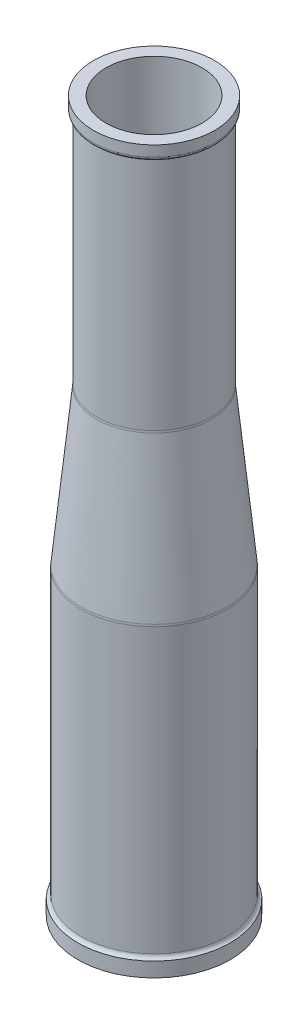
SolidWorks part; units mm, degrees
ref_plane "Alzado" through (0, 0, 0) normal (0, 0, 1) x (1, 0, 0)
ref_plane "Planta" through (0, 0, 0) normal (0, 1, 0) x (1, 0, 0)
ref_plane "Vista lateral" through (0, 0, 0) normal (1, 0, 0) x (0, 0, -1)
sketch "Croquis1" plane through (0, 0, 0) normal (0, 1, 0) x (1, 0, 0)
  circle A0 centre (0, 0) radius 35
  dimension "D1" = 70
extrude "Saliente-Extruir1" add sketch "Croquis1" along normal blind 145
ref_plane "Plano1" through (0, 220, 0) normal (0, 1, 0) x (1, 0, 0)
sketch "Croquis2" plane through (0, 220, 0) normal (0, 1, 0) x (1, 0, 0)
  circle A2 centre (0, 0) radius 27.5
  dimension "D1" = 55
loft "Recubrir1" add profiles "Croquis2" section edge at (0, 145, 35) section "Croquis2" connector at (-33.8055, 145, 9.0657) connector at (-26.1001, 220, 8.6621)
sketch "Croquis3" plane through (0, 220, 0) normal (0, 1, 0) x (1, 0, 0)
  circle A0 centre (0, 0) radius 27.5 construction
  circle A1 centre (0, 0) radius 27.5
extrude "Saliente-Extruir2" add sketch "Croquis3" along normal blind 120
sketch "Croquis5" plane through (0, 0, 0) normal (0, -1, 0) x (1, 0, 0)
  circle A0 centre (0, 0) radius 36.5
  dimension "D1" = 73
extrude "Saliente-Extruir3" add sketch "Croquis5" against normal blind 7
sketch "Croquis4" plane through (0, 0, 0) normal (0, -1, 0) x (1, 0, 0)
  circle A0 centre (0, 0) radius 23
  dimension "D1" = 46
extrude "Cortar-Extruir1" cut sketch "Croquis4" against normal blind 525
fillet "Redondeo1" radius 10 2 edges at (0, 220, 27.5) (0, 145, 35)
sketch "Croquis6" plane through (0, 340, 0) normal (0, 1, 0) x (1, 0, 0)
  circle A0 centre (0, 0) radius 29
  circle A1 centre (0, 0) radius 23 construction
  circle A2 centre (0, 0) radius 23
  dimension "D1" = 58
extrude "Saliente-Extruir4" add sketch "Croquis6" against normal blind 7
fillet "Redondeo2" radius 2 2 edges at (0, 333, 29) (0, 7, -35)
